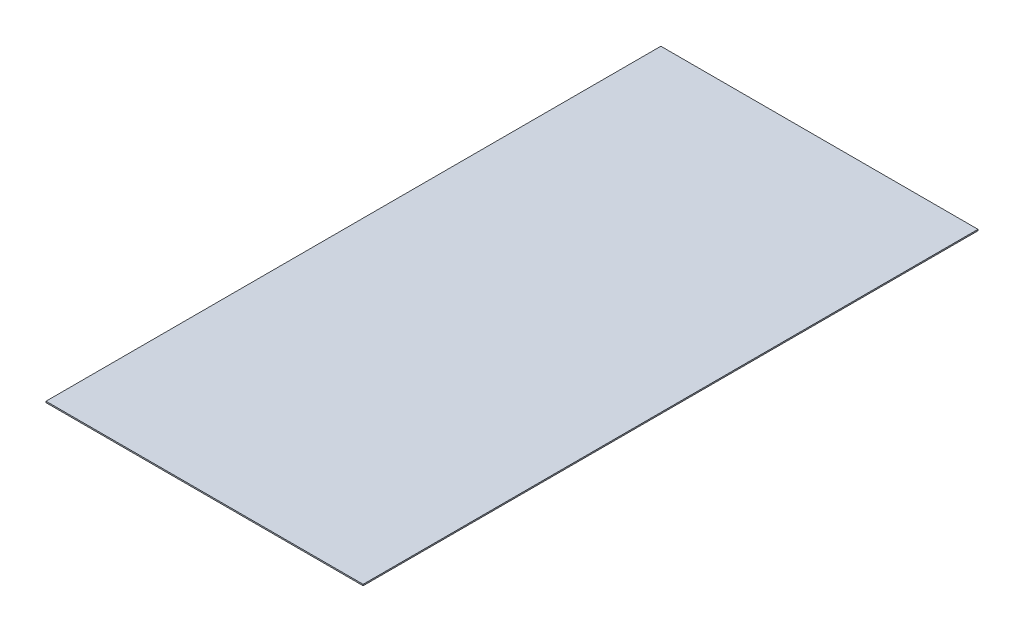
SolidWorks part; units mm, degrees
ref_plane "Front" through (0, 0, 0) normal (0, 0, 1) x (1, 0, 0)
ref_plane "Top" through (0, 0, 0) normal (0, 1, 0) x (1, 0, 0)
ref_plane "Right" through (0, 0, 0) normal (1, 0, 0) x (0, 0, -1)
sketch "Esquisse1" plane through (0, 0, 0) normal (0, 1, 0) x (1, 0, 0)
  line L1 (0, 0) -> (980, 0)
  line L2 (0, 0) -> (0, 1900)
  line L3 (0, 1900) -> (980, 1900)
  line L4 (980, 0) -> (980, 1900)
  dimension "D1" = 980
  dimension "D2" = 1900
extrude "Boss.-Extru.1" add sketch "Esquisse1" along normal blind 4
